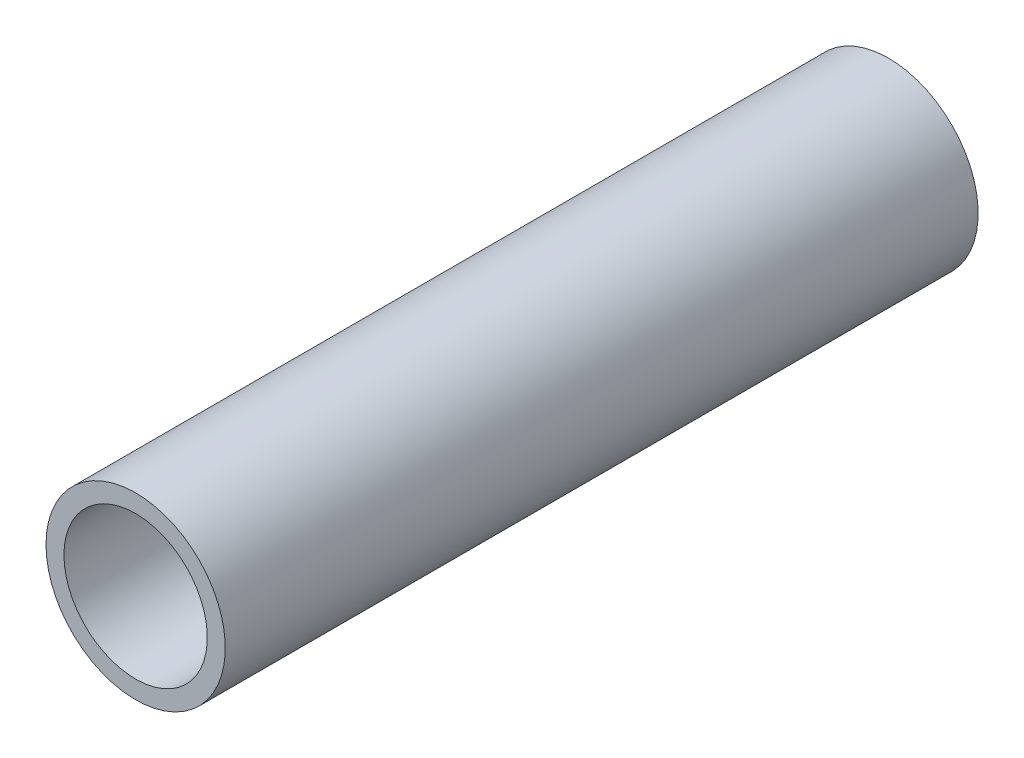
SolidWorks part; units mm, degrees
ref_plane "Front Plane" through (0, 0, 0) normal (0, 0, 1) x (1, 0, 0)
ref_plane "Top Plane" through (0, 0, 0) normal (0, 1, 0) x (1, 0, 0)
ref_plane "Right Plane" through (0, 0, 0) normal (1, 0, 0) x (0, 0, -1)
sketch "Sketch1" plane through (0, 0, 0) normal (0, 0, 1) x (1, 0, 0)
  circle A0 centre (0, 0) radius 1
  circle A1 centre (0, 0) radius 1.25
  dimension "D1" = 2
  dimension "D2" = 2.5
extrude "Tube MCP Body" add sketch "Sketch1" along normal blind 10.5
